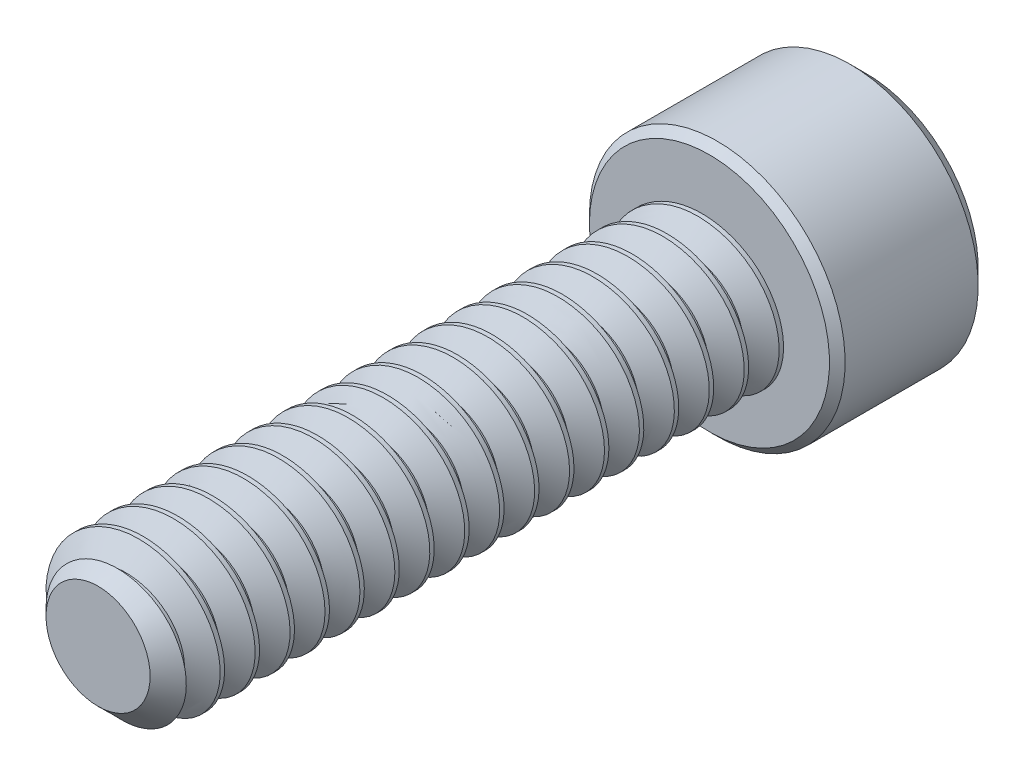
SolidWorks part; units mm, degrees
ref_plane "Front Plane" through (0, 0, 0) normal (0, 0, 1) x (1, 0, 0)
ref_plane "Top Plane" through (0, 0, 0) normal (0, 1, 0) x (1, 0, 0)
ref_plane "Right Plane" through (0, 0, 0) normal (1, 0, 0) x (0, 0, -1)
sketch "Sketch1" plane through (0, 0, 0) normal (0, 0, 1) x (1, 0, 0)
  line L0 (0, 1.4224) -> (0, -1.4224) construction
  circle A0 centre (0, 0) radius 1.4224
  dimension "OD" = 2.8448
extrude "Extrude1" add sketch "Sketch1" against normal blind 11.1125
sketch "Sketch2" plane through (0, 0, 0) normal (0, 0, 1) x (1, 0, 0)
  circle A0 centre (0, 0) radius 1.4224 construction
  circle A1 centre (0, 0) radius 1.4224
curve "Helix/Spiral1" pitch 0.635 height 11.7475 radius 1.4224 centre (0, 0, 0) axis (0, 0, -1) start towards (0, 1, 0) parameters "pitch"=0.635
chamfer "Chamfer3" distance 0.4763 angle 45 1 edges at (1.4224, 0, 0)
sketch "Sketch3" plane through (0, 0, 0) normal (1, 0, 0) x (0, 0, -1)
  line L0 (-0.5556, 1.4224) -> (-0.3175, 1.01)
  line L1 (-0.3175, 1.01) -> (-0.2381, 1.01)
  line L2 (-0.2381, 1.01) -> (0, 1.4224)
  line L3 (-0.5556, 1.4224) -> (0, 1.4224)
  line L4 (-0.2778, 1.4224) -> (-0.2778, 1.01) construction
  line L5 (-0.4366, 1.2162) -> (-0.1191, 1.2162) construction
  line L6 (0, 1.4224) -> (0, -1.4224) construction
  dimension "D1" = 0.0794
  dimension "D2" = 0.3175
  dimension "D3" = 60
sweep "Cut-Sweep1" cut profiles "Sketch3" path "Helix/Spiral1"
sketch "Sketch6" plane through (0, 0, -11.1125) normal (0, 0, -1) x (-1, 0, 0)
  circle A0 centre (0, 0) radius 2.3241
  dimension "head dia" = 4.6482
extrude "Extrude2" add sketch "Sketch6" along normal blind 2.8448
sketch "Sketch7" plane through (0, 0, -13.9573) normal (0, 0, -1) x (-1, 0, 0)
  line L1 (0, 1.3748) -> (-1.1906, 0.6874)
  line L2 (-1.1906, 0.6874) -> (-1.1906, -0.6874)
  line L3 (-1.1906, -0.6874) -> (0, -1.3748)
  line L4 (0, -1.3748) -> (1.1906, -0.6874)
  line L5 (1.1906, -0.6874) -> (1.1906, 0.6874)
  line L6 (1.1906, 0.6874) -> (0, 1.3748)
  circle A0 centre (0, 0) radius 1.1906 construction
  dimension "hex dia" = 2.3813
extrude "Cut-Extrude1" cut sketch "Sketch7" against normal blind 1.7859
sketch "Sketch8" plane through (0, 0, -13.9573) normal (0, 0, -1) x (-1, 0, 0)
  circle A0 centre (0, 0) radius 1.3748
extrude "Cut-Extrude2" cut sketch "Sketch8" against normal blind 0.2845 draft 45
chamfer "Chamfer1" distance 0.2845 angle 45 1 edges at (-2.3241, 0, -13.9573)
chamfer "Chamfer2" distance 0.1422 angle 45 1 edges at (-2.3241, 0, -11.1125)
sketch "Sketch9" plane through (0, 0, 0) normal (1, 0, 0) x (0, 0, -1)
  line L0 (0, 1.4224) -> (0, -1.4224) construction
  line L1 (3.4925, 1.4224) -> (3.4925, -1.4224) construction
  line L2 (11.1125, 2.3241) -> (11.1125, -2.3241) construction
  line L3 (13.9573, 2.3241) -> (13.9573, -2.3241) construction
  line L4 (13.9573, 0) -> (0, 0) construction
  dimension "D1" = 3.4925
  dimension "D2" = 2.8448
  dimension "D3" = 4.6482
  dimension "D4" = 11.1125
equation "\"D3@Helix/Spiral1\" = \"screw length@Extrude1\"+\"pitch@Helix/Spiral1\""
equation "\"D1@Sketch3\" = \"pitch@Helix/Spiral1\"*.125"
equation "\"D2@Sketch3\" = \"pitch@Helix/Spiral1\"*.5"
equation "\"D1@Cut-Extrude1\" = \"hex dia@Sketch7\"*.75"
equation "\"D1@Chamfer1\" = \"head depth@Extrude2\"/10"
equation "\"D1@Sketch9\" = \"pitch@Helix/Spiral1\"*5.5"
equation "\"D1@Chamfer2\" = \"D1@Chamfer1\"/2"
equation "\"D1@Cut-Extrude2\" = \"D1@Chamfer2\"*2"
equation "\"D1@Chamfer3\" = \"pitch@Helix/Spiral1\"*.750"
equation "\"D2@Sketch9\" = \"head depth@Extrude2\""
equation "\"D3@Sketch9\" = \"head dia@Sketch6\""
equation "\"D4@Sketch9\" = \"screw length@Extrude1\""
